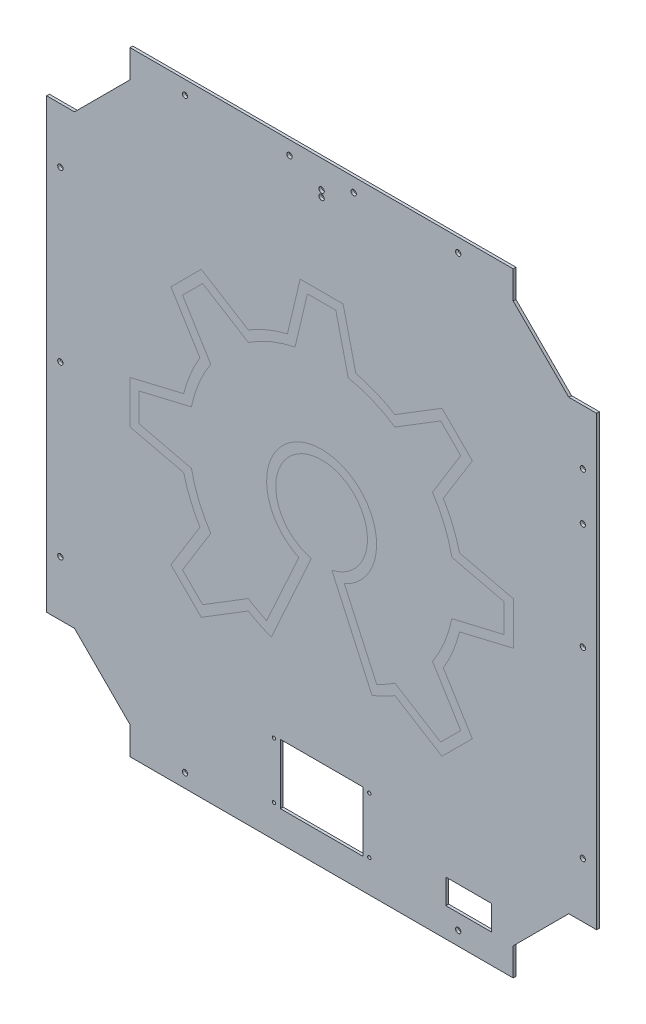
SolidWorks part; units mm, degrees
ref_plane "Front Plane" through (0, 0, 0) normal (0, 0, 1) x (1, 0, 0)
ref_plane "Top Plane" through (0, 0, 0) normal (0, 1, 0) x (1, 0, 0)
ref_plane "Right Plane" through (0, 0, 0) normal (1, 0, 0) x (0, 0, -1)
sketch "Sketch1" plane through (0, 0, 0) normal (0, 0, 1) x (1, 0, 0)
  line L1 (300, -335) -> (-300, -335)
  line L2 (300, -335) -> (300, 335)
  line L3 (300, 335) -> (-300, 335)
  line L4 (-300, -335) -> (-300, 335)
  line L5 (300, -335) -> (-300, 335) construction
  line L6 (300, 335) -> (-300, -335) construction
  point P0 (0, 0)
  dimension "D1" = 600
  dimension "D2" = 670
extrude "Boss-Extrude1" add sketch "Sketch1" along normal mid plane 3
sketch "Sketch2" plane through (0, 0, 1.5) normal (0, 0, 1) x (1, 0, 0)
  line L0 (-269.5858, 244) -> (-209, 304.5858)
  line L1 (-300, 335) -> (-209, 335)
  line L2 (-300, 335) -> (-300, 244)
  line L3 (-300, 244) -> (-269.5858, 244)
  line L4 (-209, 335) -> (-209, 304.5858)
  line L5 (300, 335) -> (209, 335)
  line L6 (300, 335) -> (300, 244)
  line L7 (300, 244) -> (269.5858, 244)
  line L8 (209, 335) -> (209, 304.5858)
  line L9 (300, -335) -> (209, -335)
  line L10 (300, -335) -> (300, -244)
  line L11 (300, -244) -> (269.5858, -244)
  line L12 (209, -335) -> (209, -304.5858)
  line L13 (-300, -335) -> (-209, -335)
  line L14 (-300, -335) -> (-300, -244)
  line L15 (-300, -244) -> (-269.5858, -244)
  line L16 (-209, -335) -> (-209, -304.5858)
  line L17 (-209, 304.5858) -> (209, 304.5858) construction
  line L18 (209, 304.5858) -> (269.5858, 244)
  line L19 (269.5858, 244) -> (269.5858, -244) construction
  line L20 (269.5858, -244) -> (209, -304.5858)
  line L21 (209, -304.5858) -> (-209, -304.5858) construction
  line L22 (-209, -304.5858) -> (-269.5858, -244)
  line L23 (-269.5858, -244) -> (-269.5858, 244) construction
  line L24 (-300, 305) -> (-209, 305) construction
  line L25 (-210, 335) -> (-210, 305) construction
  line L26 (-210, 305) -> (-240.7756, 274.2244) construction
  dimension "D1" = 91
  dimension "D2" = 30
  dimension "D3" = 1
  dimension "D4" = 1
extrude "Cut-Extrude1" cut sketch "Sketch2" against normal through all
hole_wizard "M5 Clearance Hole1" positions "Sketch3" profile "Sketch4" hole size "M5" standard "DIN" end condition through all
sketch "Sketch3" plane through (0, 0, 1.5) normal (0, 0, 1) x (1, 0, 0)
  line L0 (-149, 320) -> (149, 320) construction
  line L1 (149, 320) -> (149, -320) construction
  line L2 (149, -320) -> (-149, -320) construction
  line L3 (-149, -320) -> (-149, 320) construction
  line L5 (-285, 184) -> (285, 184) construction
  line L6 (285, 184) -> (285, 15.545) construction
  line L7 (285, 15.545) -> (285, -184) construction
  line L8 (285, -184) -> (-285, -184) construction
  line L9 (-285, -184) -> (-285, 0) construction
  line L10 (-285, 0) -> (-285, 184) construction
  line L13 (0, 320) -> (0, -320) construction
  line L15 (-300, 0) -> (-285, 0) construction
  line L16 (-300, 244) -> (-300, -244) construction
  line L18 (-300, 244) -> (-269.5858, 244) construction
  line L19 (209, 335) -> (-209, 335) construction
  line L20 (-209, 304.5858) -> (-209, 335) construction
  point P0 (-149, 320)
  point P2 (149, 320)
  point P4 (-285, 184)
  point P6 (-285, 0)
  point P8 (-285, -184)
  point P10 (285, -184)
  point P12 (285, 15.545)
  point P14 (285, 184)
  point P16 (149, -320)
  point P18 (-149, -320)
  point P20 (285, 132)
  point P58 (0, 184)
  point P67 (0, 0)
  point P68 (285, 132)
  dimension "D1" = 15
  dimension "D2" = 60
  dimension "D3" = 15
  dimension "D4" = 60
  dimension "D5" = 52
sketch "Sketch4" plane through (-149, 320, 1.5) normal (1, 0, 0) x (0, -1, 0)
  line L0 (0, 0) -> (0, 3)
  line L1 (0, 3) -> (2.9, 3)
  line L2 (2.9, 3) -> (2.9, 0)
  line L5 (2.9, 0) -> (0, 0)
  line L11 (0, -6.35) -> (0, 107.95) construction
  dimension "Thru Hole Dia." = 5.8
  dimension "Thru Hole Depth" = 3
hole_wizard "M5 Clearance Hole2" positions "Sketch5" profile "Sketch6" hole size "M5" standard "DIN" end condition through all
sketch "Sketch5" plane through (0, 0, 1.5) normal (0, 0, 1) x (1, 0, 0)
  line L0 (-149, 320) -> (-35, 320) construction
  line L1 (-35, 320) -> (35, 320) construction
  line L2 (35, 320) -> (149, 320) construction
  line L4 (0, 320) -> (0, 305) construction
  line L5 (0, 305) -> (0, 298) construction
  line L7 (209, 335) -> (-209, 335) construction
  point P0 (-35, 320)
  point P2 (35, 320)
  point P4 (0, 305)
  point P6 (0, 298)
  point P24 (-11.2021, 320)
  point P25 (47.3515, 320)
  point P26 (-0.9524, 320)
  point P27 (38.4224, 320)
  dimension "D1" = 30
  dimension "D2" = 7
  dimension "D3" = 70
sketch "Sketch6" plane through (-35, 320, 1.5) normal (1, 0, 0) x (0, -1, 0)
  line L0 (0, 0) -> (0, 3)
  line L1 (0, 3) -> (2.9, 3)
  line L2 (2.9, 3) -> (2.9, 0)
  line L5 (2.9, 0) -> (0, 0)
  line L11 (0, -6.35) -> (0, 107.95) construction
  dimension "Thru Hole Dia." = 5.8
  dimension "Thru Hole Depth" = 3
sketch "Sketch7" plane through (0, 0, 1.5) normal (0, 0, 1) x (1, 0, 0)
  line L0 (0, 0) -> (0, -236.5) construction
  line L1 (-45, -302) -> (45, -302)
  line L2 (-45, -302) -> (-45, -236.5)
  line L3 (-45, -236.5) -> (45, -236.5)
  line L4 (45, -302) -> (45, -236.5)
  line L5 (-209, -335) -> (209, -335) construction
  dimension "D1" = 90
  dimension "D2" = 33
  dimension "D3" = 65.5
extrude "Cut-Extrude2" cut sketch "Sketch7" against normal through all
hole_wizard "M3 Clearance Hole1" positions "Sketch9" profile "Sketch10" hole size "M3" standard "DIN" end condition through all
sketch "Sketch9" plane through (0, 0, -1.5) normal (0, 0, -1) x (-1, 0, 0)
  line L1 (-52, -238.75) -> (52, -238.75) construction
  line L2 (-52, -238.75) -> (-52, -299.75) construction
  line L3 (-52, -299.75) -> (52, -299.75) construction
  line L4 (52, -238.75) -> (52, -299.75) construction
  line L5 (-45, -236.5) -> (45, -302) construction
  line L7 (-52, -299.75) -> (52, -238.75) construction
  point P0 (-52, -238.75)
  point P2 (52, -238.75)
  point P4 (-52, -299.75)
  point P6 (52, -299.75)
  point P112 (0, -269.25)
  point P113 (-51.6356, -244.8765)
  dimension "D1" = 104
  dimension "D2" = 61
sketch "Sketch10" plane through (52, -238.75, -1.5) normal (1, 0, 0) x (0, 1, 0)
  line L0 (0, 0) -> (0, 3)
  line L1 (0, 3) -> (1.8, 3)
  line L2 (1.8, 3) -> (1.8, 0)
  line L5 (1.8, 0) -> (0, 0)
  line L11 (0, -6.35) -> (0, 107.95) construction
  dimension "Thru Hole Dia." = 3.6
  dimension "Thru Hole Depth" = 3
sketch "Sketch11" plane through (0, 0, 1.5) normal (0, 0, 1) x (1, 0, 0)
  line L0 (-209, -335) -> (209, -335) construction
  line L1 (135.5, -276.4) -> (185.5, -276.4)
  line L2 (135.5, -276.4) -> (135.5, -303.4)
  line L3 (135.5, -303.4) -> (185.5, -303.4)
  line L4 (185.5, -276.4) -> (185.5, -303.4)
  line L5 (209, -304.5858) -> (209, -335) construction
  dimension "D1" = 50
  dimension "D2" = 27
  dimension "D3" = 31.6
  dimension "D4" = 23.5
extrude "Cut-Extrude3" cut sketch "Sketch11" against normal through all
sketch "Sketch13" plane through (0, 0, 1.5) normal (0, 0, 1) x (1, 0, 0)
  line L0 (-29, 142.0704) -> (29, 142.0704) construction
  line L1 (0, 142.0704) -> (0, 0) construction
  line L2 (0, 142.0704) -> (0, 199.0704) construction
  line L3 (-15.5, 199.0704) -> (15.5, 199.0704)
  line L4 (-15.5, 199.0704) -> (-29, 142.0704)
  line L5 (15.5, 199.0704) -> (29, 142.0704)
  line L6 (129.8039, 151.7242) -> (79.9529, 120.965)
  line L7 (129.8039, 151.7242) -> (151.7242, 129.8039)
  line L8 (151.7242, 129.8039) -> (120.965, 79.9529)
  line L9 (199.0704, 15.5) -> (142.0704, 29)
  line L10 (199.0704, 15.5) -> (199.0704, -15.5)
  line L11 (199.0704, -15.5) -> (142.0704, -29)
  line L12 (151.7242, -129.8039) -> (120.965, -79.9529)
  line L13 (151.7242, -129.8039) -> (129.8039, -151.7242)
  line L14 (129.8039, -151.7242) -> (79.9529, -120.965)
  line L15 (-24.8276, -54.6223) -> (-60, -132.0038)
  line L16 (-60, -132.0038) -> (60, -132.0038) construction
  line L17 (60, -132.0038) -> (24.8276, -54.6223)
  line L18 (-129.8039, -151.7242) -> (-79.9529, -120.965)
  line L19 (-129.8039, -151.7242) -> (-151.7242, -129.8039)
  line L20 (-151.7242, -129.8039) -> (-120.965, -79.9529)
  line L21 (-199.0704, -15.5) -> (-142.0704, -29)
  line L22 (-199.0704, -15.5) -> (-199.0704, 15.5)
  line L23 (-199.0704, 15.5) -> (-142.0704, 29)
  line L24 (-151.7242, 129.8039) -> (-120.965, 79.9529)
  line L25 (-151.7242, 129.8039) -> (-129.8039, 151.7242)
  line L26 (-129.8039, 151.7242) -> (-79.9529, 120.965)
  line L27 (0, 0) -> (-140.764, 140.764) construction
  line L28 (0, 0) -> (0, -132.0038) construction
  line L29 (-15.5, -199.0704) -> (-29, -142.0704) [skipped]
  line L30 (15.5, -199.0704) -> (29, -142.0704) [skipped]
  line L31 (15.5, -199.0704) -> (-15.5, -199.0704) [skipped]
  line L32 (0, 0) -> (-24.8276, -54.6223) construction
  line L33 (-24.8276, -54.6223) -> (24.8276, -54.6223) construction
  line L34 (24.8276, -54.6223) -> (0, 0) construction
  arc A0 (24.8276, -54.6223) -> (-24.8276, -54.6223) centre (0, 0) ccw
  arc A1 (-29, 142.0704) -> (-79.9529, 120.965) centre (0, 0) ccw
  arc A2 (-120.965, 79.9529) -> (-142.0704, 29) centre (0, 0) ccw
  arc A3 (-142.0704, -29) -> (-120.965, -79.9529) centre (0, 0) ccw
  arc A4 (-79.9529, -120.965) -> (-60, -132.0038) centre (0, 0) ccw
  arc A5 (120.965, -79.9529) -> (142.0704, -29) centre (0, 0) ccw
  arc A6 (142.0704, 29) -> (120.965, 79.9529) centre (0, 0) ccw
  arc A7 (79.9529, 120.965) -> (29, 142.0704) centre (0, 0) ccw
  arc A8 (60, -132.0038) -> (79.9529, -120.965) centre (0, 0) ccw
  dimension "D1" = 120
  dimension "D2" = 290
  dimension "D3" = 58
  dimension "D4" = 31
  dimension "D5" = 57
  dimension "D7" = 45
  dimension "D8" = 120
  dimension "D6" = 8
wrap "Wrap1" sketch "Sketch13" wrap type scribe source sketch "Sketch13" face at (160.5, -289.9, 1.5)
sketch "Sketch14" plane through (0, 0, 1.5) normal (0, 0, 1) x (1, 0, 0)
  line L46 (-23.4082, 209.0704) -> (-37.2928, 150.4468)
  line L47 (-80.012, 132.7519) -> (-131.283, 164.3872)
  line L48 (-131.283, 164.3872) -> (-164.3872, 131.283)
  line L49 (-164.3872, 131.283) -> (-132.7519, 80.012)
  line L50 (-150.4468, 37.2928) -> (-209.0704, 23.4082)
  line L51 (-209.0704, 23.4082) -> (-209.0704, -23.4082)
  line L52 (-209.0704, -23.4082) -> (-150.4468, -37.2928)
  line L53 (-132.7519, -80.012) -> (-164.3872, -131.283)
  line L54 (-164.3872, -131.283) -> (-131.283, -164.3872)
  line L55 (-131.283, -164.3872) -> (-80.012, -132.7519)
  line L56 (-54.9006, -144.9515) -> (-11.1679, -48.7368)
  line L57 (11.1679, -48.7368) -> (54.9006, -144.9515)
  line L58 (80.012, -132.7519) -> (131.283, -164.3872)
  line L59 (131.283, -164.3872) -> (164.3872, -131.283)
  line L60 (164.3872, -131.283) -> (132.7519, -80.012)
  line L61 (150.4468, -37.2928) -> (209.0704, -23.4082)
  line L62 (209.0704, -23.4082) -> (209.0704, 23.4082)
  line L63 (209.0704, 23.4082) -> (150.4468, 37.2928)
  line L64 (132.7519, 80.012) -> (164.3872, 131.283)
  line L65 (164.3872, 131.283) -> (131.283, 164.3872)
  line L66 (131.283, 164.3872) -> (80.012, 132.7519)
  line L67 (37.2928, 150.4468) -> (23.4082, 209.0704)
  line L68 (23.4082, 209.0704) -> (-23.4082, 209.0704)
  line L69 (-23.4082, 209.0704) -> (-37.2928, 150.4468)
  line L70 (-80.012, 132.7519) -> (-131.283, 164.3872)
  line L71 (-131.283, 164.3872) -> (-164.3872, 131.283)
  line L72 (-164.3872, 131.283) -> (-132.7519, 80.012)
  line L73 (-150.4468, 37.2928) -> (-209.0704, 23.4082)
  line L74 (-209.0704, 23.4082) -> (-209.0704, -23.4082)
  line L75 (-209.0704, -23.4082) -> (-150.4468, -37.2928)
  line L76 (-132.7519, -80.012) -> (-164.3872, -131.283)
  line L77 (-164.3872, -131.283) -> (-131.283, -164.3872)
  line L78 (-131.283, -164.3872) -> (-80.012, -132.7519)
  line L79 (-54.9006, -144.9515) -> (-11.1679, -48.7368)
  line L80 (11.1679, -48.7368) -> (54.9006, -144.9515)
  line L81 (80.012, -132.7519) -> (131.283, -164.3872)
  line L82 (131.283, -164.3872) -> (164.3872, -131.283)
  line L83 (164.3872, -131.283) -> (132.7519, -80.012)
  line L84 (150.4468, -37.2928) -> (209.0704, -23.4082)
  line L85 (209.0704, -23.4082) -> (209.0704, 23.4082)
  line L86 (209.0704, 23.4082) -> (150.4468, 37.2928)
  line L87 (132.7519, 80.012) -> (164.3872, 131.283)
  line L88 (164.3872, 131.283) -> (131.283, 164.3872)
  line L89 (131.283, 164.3872) -> (80.012, 132.7519)
  line L90 (37.2928, 150.4468) -> (23.4082, 209.0704)
  line L91 (23.4082, 209.0704) -> (-23.4082, 209.0704)
  arc A18 (-37.2928, 150.4468) -> (-80.012, 132.7519) centre (0, 0) ccw
  arc A19 (-132.7519, 80.012) -> (-150.4468, 37.2928) centre (0, 0) ccw
  arc A20 (-150.4468, -37.2928) -> (-132.7519, -80.012) centre (0, 0) ccw
  arc A21 (-80.012, -132.7519) -> (-54.9006, -144.9515) centre (0, 0) ccw
  arc A22 (11.1679, -48.7368) -> (-11.1679, -48.7368) centre (0, 0) ccw
  arc A23 (54.9006, -144.9515) -> (80.012, -132.7519) centre (0, 0) ccw
  arc A24 (132.7519, -80.012) -> (150.4468, -37.2928) centre (0, 0) ccw
  arc A25 (150.4468, 37.2928) -> (132.7519, 80.012) centre (0, 0) ccw
  arc A26 (80.012, 132.7519) -> (37.2928, 150.4468) centre (0, 0) ccw
  arc A27 (-37.2928, 150.4468) -> (-80.012, 132.7519) centre (0, 0) ccw
  arc A28 (-132.7519, 80.012) -> (-150.4468, 37.2928) centre (0, 0) ccw
  arc A29 (-150.4468, -37.2928) -> (-132.7519, -80.012) centre (0, 0) ccw
  arc A30 (-80.012, -132.7519) -> (-54.9006, -144.9515) centre (0, 0) ccw
  arc A31 (11.1679, -48.7368) -> (-11.1679, -48.7368) centre (0, 0) ccw
  arc A32 (54.9006, -144.9515) -> (80.012, -132.7519) centre (0, 0) ccw
  arc A33 (132.7519, -80.012) -> (150.4468, -37.2928) centre (0, 0) ccw
  arc A34 (150.4468, 37.2928) -> (132.7519, 80.012) centre (0, 0) ccw
  arc A35 (80.012, 132.7519) -> (37.2928, 150.4468) centre (0, 0) ccw
  dimension "D1" = 10
wrap "Wrap2" sketch "Sketch14" wrap type scribe source sketch "Sketch14" face at (0, 13.3674, 1.5)
